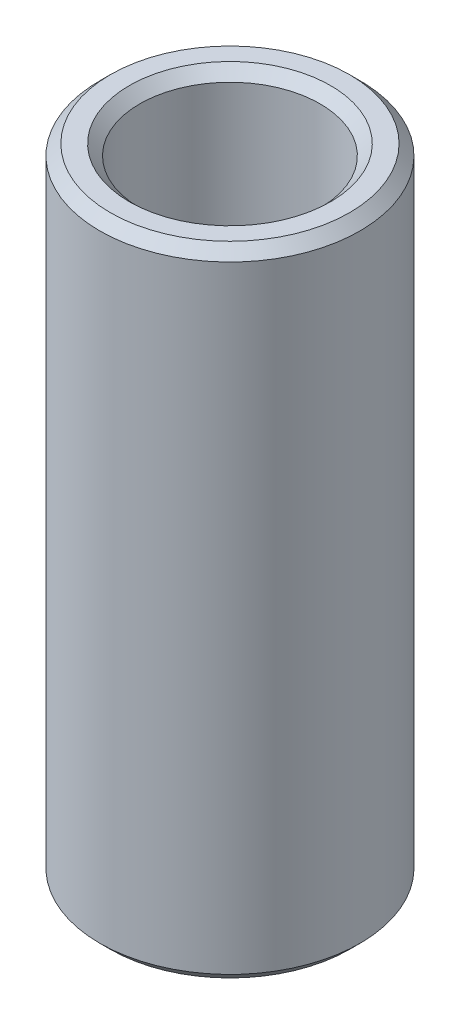
SolidWorks part; units mm, degrees
ref_plane "Front Plane" through (0, 0, 0) normal (0, 0, 1) x (1, 0, 0)
ref_plane "Top Plane" through (0, 0, 0) normal (0, 1, 0) x (1, 0, 0)
ref_plane "Right Plane" through (0, 0, 0) normal (1, 0, 0) x (0, 0, -1)
sketch "Sketch1" plane through (0, 0, 0) normal (0, 1, 0) x (1, 0, 0)
  circle A0 centre (0, 0) radius 30
  dimension "SLEEVE_OD" = 60
extrude "Boss-Extrude1" add sketch "Sketch1" along normal blind 147.0864
sketch "Sketch2" plane through (0, 0, 0) normal (0, 1, 0) x (1, 0, 0)
  circle A0 centre (0, 0) radius 20.7809
  dimension "BORE_D" = 41.5617
extrude "Cut-Extrude1" cut sketch "Sketch2" along normal through all
chamfer "Chamfer1" distance 2.4266 angle 45 4 edges at (0, 147.0864, 20.7809) (0, 0, 20.7809) (0, 0, 30) (0, 147.0864, 30)
